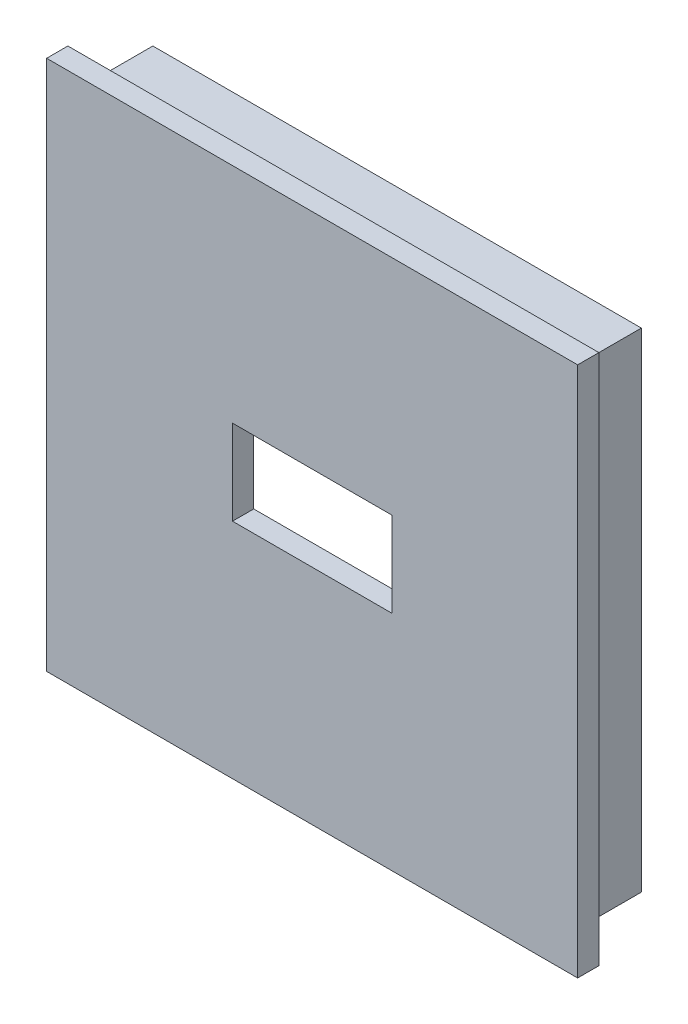
SolidWorks part; units mm, degrees
ref_plane "Front Plane" through (0, 0, 0) normal (0, 0, 1) x (1, 0, 0)
ref_plane "Top Plane" through (0, 0, 0) normal (0, 1, 0) x (1, 0, 0)
ref_plane "Right Plane" through (0, 0, 0) normal (1, 0, 0) x (0, 0, -1)
sketch "Sketch1" plane through (0, 0, 0) normal (0, 0, 1) x (1, 0, 0)
  line L1 (-12.5, -12.5) -> (12.5, -12.5)
  line L2 (-12.5, -12.5) -> (-12.5, 12.5)
  line L3 (-12.5, 12.5) -> (12.5, 12.5)
  line L4 (12.5, -12.5) -> (12.5, 12.5)
  line L5 (-12.5, -12.5) -> (12.5, 12.5) construction
  line L6 (-12.5, 12.5) -> (12.5, -12.5) construction
  point P0 (0, 0)
  dimension "D1" = 25
  dimension "D2" = 25
extrude "Boss-Extrude1" add sketch "Sketch1" along normal blind 1
sketch "Sketch2" plane through (0, 0, 0) normal (0, 0, -1) x (-1, 0, 0)
  line L1 (-11.5, -11.5) -> (11.5, -11.5)
  line L2 (-11.5, -11.5) -> (-11.5, 11.5)
  line L3 (-11.5, 11.5) -> (11.5, 11.5)
  line L4 (11.5, -11.5) -> (11.5, 11.5)
  line L5 (-11.5, -11.5) -> (11.5, 11.5) construction
  line L6 (-11.5, 11.5) -> (11.5, -11.5) construction
  point P0 (0, 0)
  dimension "D1" = 23
  dimension "D2" = 23
extrude "Boss-Extrude2" add sketch "Sketch2" along normal blind 3
shell "Shell1" thickness 1 removed face at (0, 0, -3)
sketch "Sketch3" plane through (0, 0, 0) normal (0, 0, -1) x (-1, 0, 0)
  line L1 (-3.75, -2) -> (3.75, -2)
  line L2 (-3.75, -2) -> (-3.75, 2)
  line L3 (-3.75, 2) -> (3.75, 2)
  line L4 (3.75, -2) -> (3.75, 2)
  line L5 (-3.75, -2) -> (3.75, 2) construction
  line L6 (-3.75, 2) -> (3.75, -2) construction
  point P0 (0, 0)
  dimension "D1" = 4
  dimension "D2" = 7.5
extrude "Cut-Extrude1" cut sketch "Sketch3" against normal blind 10
